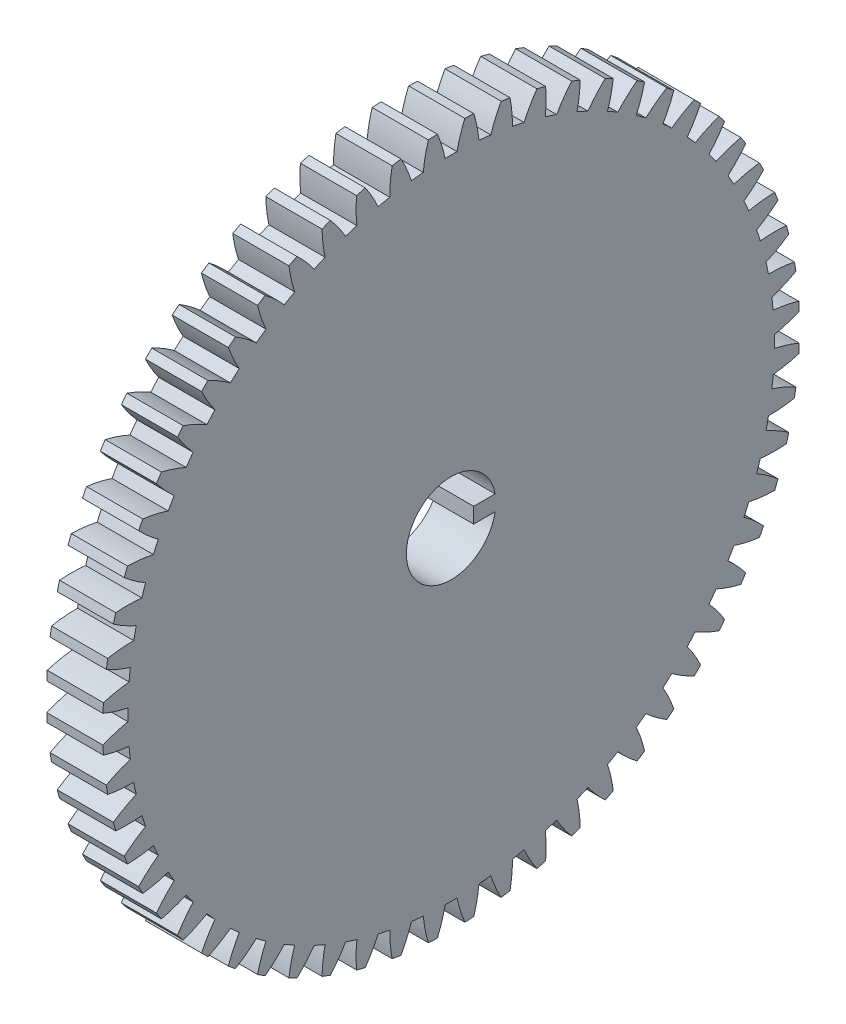
SolidWorks part; units mm, degrees
ref_plane "Plane1" through (0, 0, 0) normal (0, 0, 1) x (1, 0, 0)
ref_plane "Plane2" through (0, 0, 0) normal (0, 1, 0) x (1, 0, 0)
ref_plane "Plane3" through (0, 0, 0) normal (1, 0, 0) x (0, 0, -1)
sketch "HoldingSke" plane through (0, 0, 0) normal (0, 1, 0) x (1, 0, 0)
  line L0 (0, 0) -> (254, -439.9409)
  line L1 (-15, 0) -> (100, 0) construction
  line L2 (0, 0) -> (-2.1039, 2.3779)
  line L3 (0, 0) -> (-11.863, 4.5341)
  line L4 (0, 0) -> (4.318, 7.479)
  line L5 (0, 0) -> (-47.5972, -17.7524)
  line L6 (0, 0) -> (-5.2639, -3.5516)
  line L7 (-2.1039, 2.3779) -> (8.8308, 51.9871)
  line L8 (-76.2, 54.61) -> (-65.4837, 54.61)
  line L9 (-67.7845, 28.3722) -> (-49.3413, 33.142)
  line L10 (-76.2, 71.12) -> (104.1128, 71.12)
  line L11 (0, 0) -> (-6.35, 0)
  line L12 (-76.2, 101.6) -> (-76.1492, 101.6)
  line L13 (24.9733, 27.94) -> (52.9518, 28.4284)
  line L14 (24.9733, 27.94) -> (25.0241, 27.9398)
  line L15 (24.9733, 27.94) -> (100.4021, 29.52)
  circle A0 centre (0, 0) radius 4.7625
  circle A1 centre (0, 0) radius 36.5252
  circle A2 centre (0, 0) radius 38.1
  circle A3 centre (0, 0) radius 4.7625
  dimension "Num_teeth" = 60
  dimension "H" = 19.05
  dimension "Pitch_radius" = 180.3128
  dimension "Width" = 6.35
  dimension "Thickness" = 6.35
sketch "BasProSke" plane through (0, 0, 0) normal (0, 1, 0) x (1, 0, 0)
  line L0 (-10, 0) -> (60, 0) construction
  line L1 (0, 0) -> (0, 39.37)
  line L2 (0, 0) -> (6.35, 0)
  line L3 (6.35, 0) -> (6.35, 39.37)
  line L4 (6.35, 39.37) -> (0, 39.37)
  dimension "Thickness" = 6.35
  dimension "Diameter" = 78.74
revolve "Base-Revolve" add sketch "BasProSke" angle 360 about L0
sketch "TooCutSke" plane through (0, 0, 0) normal (1, 0, 0) x (0, 0, -1)
  line L1 (0, 0) -> (0, 107) construction
  line L2 (0, 0) -> (-1.0862, 38.0845) construction
  line L3 (0, 0) -> (-3.9869, 76.0739) construction
  line L4 (-1.0862, 38.0845) -> (-1.9934, 38.037) construction
  arc A0 (0.674, 36.519) -> (-0.674, 36.519) centre (0, 0) ccw
  arc A1 (1.5613, 39.3644) -> (-1.5613, 39.3644) centre (0, 0) ccw
  circle A2 centre (0, 0) radius 38.1 construction
  circle A3 centre (0, 0) radius 36.8864 construction
  arc A4 (-0.674, 36.519) -> (-1.5613, 39.3644) centre (-15.597, 33.4267) ccw
  arc A5 (1.5613, 39.3644) -> (0.674, 36.519) centre (15.597, 33.4267) ccw
extrude "ToothCut" cut sketch "TooCutSke" along normal through all
fillet "Breaks" [suppressed] radius 0.0254 tangent propagation no
fillet "RootFillets" [suppressed] radius 0.3048
pattern_circular "TeethCuts" count 60 every 6 about axis through (-10, 0, 0) along (1, 0, 0) of "ToothCut", "RootFillets", "Breaks"
sketch "HubNeaOneSke" plane through (0, 0, 0) normal (-1, 0, 0) x (0, 0, 1)
  circle A0 centre (0, 0) radius 36.5252
  dimension "Diameter" = 73.0504
extrude "HubNearOne" [suppressed] add sketch "HubNeaOneSke" along normal blind 44.4501
sketch "HubNeaBotSke" plane through (0, 0, 0) normal (-1, 0, 0) x (0, 0, 1)
  circle A0 centre (0, 0) radius 36.5252
  dimension "Diameter" = 73.0504
extrude "HubNearBoth" [suppressed] add sketch "HubNeaBotSke" along normal blind 22.225
ref_plane "FarPln" through (6.35, 0, 0) normal (1, 0, 0) x (0, 0, -1)
sketch "HubFarSke" plane through (6.35, 0, 0) normal (1, 0, 0) x (0, 0, -1)
  circle A0 centre (0, 0) radius 36.5252
  dimension "Diameter" = 73.0504
extrude "HubFar" [suppressed] add sketch "HubFarSke" along normal blind 22.225
sketch "BorSke" plane through (0, 0, 0) normal (1, 0, 0) x (0, 0, -1)
  circle A0 centre (0, 0) radius 5.05
  dimension "D1" = 10.1
extrude "Bore" cut sketch "BorSke" along normal mid plane 101.6001
sketch "KeySke" plane through (0, 0, 0) normal (1, 0, 0) x (0, 0, -1)
  line L0 (-1.1913, 0) -> (-1.1913, 5.9538)
  line L1 (-1.1913, 5.9538) -> (1.1913, 5.9538)
  line L2 (1.1913, 5.9538) -> (1.1913, 0)
  line L3 (0, 0) -> (0, 34) construction
  line L4 (-1.1913, 0) -> (1.1913, 0)
  dimension "Width" = 2.3825
extrude "Keyway" [suppressed] cut sketch "KeySke" along normal mid plane 101.6001
pattern_circular "Keyway2" [suppressed] count 2 every 90 about axis through (-10, 0, 0) along (1, 0, 0) reverse direction yes
sketch "Sketch1" plane through (6.35, 0, 0) normal (1, 0, 0) x (0, 0, -1)
  line L0 (5.05, 0) -> (2.55, 0) construction
  line L1 (2.55, -0.875) -> (2.55, 0.875)
  line L2 (2.55, 0.875) -> (4.9736, 0.875)
  line L3 (2.55, -0.875) -> (4.9736, -0.875)
  circle A0 centre (0, 0) radius 5.05 construction
  circle A1 centre (0, 0) radius 5.05
  point P8 (2.55, 0)
  dimension "D1" = 2.5
  dimension "D2" = 1.75
extrude "Boss-Extrude1" add sketch "Sketch1" against normal blind 6.35 contours L0 A1 L2 L1 | A1 L0 L1 L3 region at (6.35, -0.4353, -3.7874) region at (6.35, 0.4353, -3.7874)
equation "' \"Pitch@HoldingSke\" = 4"
equation "' \"Num_teeth@HoldingSke\" = 12"
equation "' \"Ap@HoldingSke\" =  20"
equation "' \"Ap@HoldingSke\" = 20"
equation "' \"Width@HoldingSke\" = 0.5"
equation "' \"Hub_dia@HoldingSke\"= 1"
equation "' \"Hub_dia@HoldingSke\" = 1"
equation "' \"Overall_len@HoldingSke\" = 1.0"
equation "' \"Bore@HoldingSke\" = 0.75"
equation "' \"T_dim@HoldingSke\" = 0.85"
equation "' \"Width@KeySke\" = 0.25"
equation "' \"Show_teeth@HoldingSke\" = 13"
equation "' \"Backlash@HoldingSke\" = 0.009"
equation "' \"Addendum_fac@HoldingSke\" = 1.0"
equation "' \"Dedendum_fac@HoldingSke\" = 1.25"
equation "' \"Dedendum_add@HoldingSke\" = 0.00005"
equation "' \"Clearance_fac@HoldingSke\" = 0.25"
equation "' \"Pitch@HoldingSke\" = 0.5"
equation "' \"Num_teeth@HoldingSke\" = 23"
equation "' \"Show_teeth@HoldingSke\" = 23"
equation "' \"Backlash@HoldingSke\" = 0.0375"
equation "\"Overcut_dia@TooCutSke\" = (\"Num_teeth@HoldingSke\" + 2 * \"Addendum_fac@HoldingSke\") / \"Pitch@HoldingSke\" + 0.002"
equation "\"Pitch_dia@TooCutSke\" = \"Num_teeth@HoldingSke\" / \"Pitch@HoldingSke\""
equation "\"Base_dia@TooCutSke\" = \"Num_teeth@HoldingSke\" / \"Pitch@HoldingSke\" * cos((\"Ap@HoldingSke\"  * 3.14159265 / 180))"
equation "\"Root_dia@TooCutSke\" = (\"Num_teeth@HoldingSke\" + 2) / \"Pitch@HoldingSke\" - 2 * (\"Addendum_fac@HoldingSke\" + \"Dedendum_fac@HoldingSke\") / \"Pitch@HoldingSke\" - \"Dedendum_add@HoldingSke\" * 2"
equation "\"Half_ang@TooCutSke\" = 180 / \"Num_teeth@HoldingSke\""
equation "\"Half_CT@TooCutSke\" = \"Num_teeth@HoldingSke\" / \"Pitch@HoldingSke\" * sin((3.14159265 / 2 / \"Num_teeth@HoldingSke\")) / 2 - 7 * \"Backlash@HoldingSke\" / 4"
equation "\"Flank_rad@TooCutSke\" = \"Num_teeth@HoldingSke\" / \"Pitch@HoldingSke\" / 5"
equation "\"Radius@RootFillets\" = \"Clearance_fac@HoldingSke\" / \"Pitch@HoldingSke\" + \"Dedendum_add@HoldingSke\""
equation "\"Break_rad@Breaks\" = 0.02 / \"Pitch@HoldingSke\""
equation "\"Thickness@HoldingSke\" = \"Width@HoldingSke\""
equation "\"OAL@HoldingSke\" = \"Thickness@HoldingSke\""
equation "\"MHD@HoldingSke\" = (\"Num_teeth@HoldingSke\" + 2) / \"Pitch@HoldingSke\" - 2 * (\"Addendum_fac@HoldingSke\" + \"Dedendum_fac@HoldingSke\")  / \"Pitch@HoldingSke\" - \"Dedendum_add@HoldingSke\" * 2"
equation "\"MBD@HoldingSke\" = (\"Num_teeth@HoldingSke\" + 2) / \"Pitch@HoldingSke\" - 2 * (\"Addendum_fac@HoldingSke\" + \"Dedendum_fac@HoldingSke\")  / \"Pitch@HoldingSke\" - \"Dedendum_add@HoldingSke\" * 2 - 0.002"
equation "\"MHD@HoldingSke\" = ((sgn( \"MHD@HoldingSke\" - \"Hub_dia@HoldingSke\" )-1)*( \"MHD@HoldingSke\" - \"Hub_dia@HoldingSke\" ))/-2+ \"Hub_dia@HoldingSke\""
equation "\"MBD@HoldingSke\" = ((sgn( \"MBD@HoldingSke\" - \"Bore@HoldingSke\" )-1)*( \"MBD@HoldingSke\" - \"Bore@HoldingSke\" ))/-2+ \"Bore@HoldingSke\""
equation "\"OAL@HoldingSke\" = ((sgn( \"OAL@HoldingSke\" - \"Overall_len@HoldingSke\" )+1)*( \"OAL@HoldingSke\" - \"Overall_len@HoldingSke\" ))/2 + \"Overall_len@HoldingSke\" + 0.000002"
equation "\"Num_teeth@TeethCuts\" = int( \"Show_teeth@HoldingSke\" ) + 1"
equation "\"Num_teeth@TeethCuts\" = ((sgn( \"Num_teeth@TeethCuts\" - \"Num_teeth@HoldingSke\" )-1)*( \"Num_teeth@TeethCuts\" - \"Num_teeth@HoldingSke\" ))/-2+ \"Num_teeth@HoldingSke\""
equation "\"Num_teeth@TeethCuts\" = ((sgn( \"Num_teeth@TeethCuts\" - 2.0)+1)*( \"Num_teeth@TeethCuts\" - 2.0))/2 +2.0"
equation "\"Angle@TeethCuts\" = 360.0 / \"Num_teeth@HoldingSke\""
equation "\"Diameter@BasProSke\" = (\"Num_teeth@HoldingSke\" + 2 * \"Addendum_fac@HoldingSke\") / \"Pitch@HoldingSke\""
equation "\"Thickness@BasProSke\"  = \"Thickness@HoldingSke\""
equation "' \"Fillet_rad@BasProSke\" =  \"Thickness@HoldingSke\" * 0.05"
equation "' \"Fillet_rad@BasProSke\" = \"Thickness@HoldingSke\" * 0.05"
equation "\"MHD@HoldingSke\" = ((sgn( \"MHD@HoldingSke\" - \"Root_dia@TooCutSke\" )-1)*( \"MHD@HoldingSke\" - \"Root_dia@TooCutSke\" ))/-2+ \"Root_dia@TooCutSke\""
equation "\"Diameter@HubNeaOneSke\" = \"MHD@HoldingSke\""
equation "\"Length@HubNearOne\" = \"OAL@HoldingSke\" - \"Thickness@BasProSke\""
equation "\"Diameter@HubNeaBotSke\" = \"MHD@HoldingSke\""
equation "\"Length@HubNearBoth\" = ( \"OAL@HoldingSke\" - \"Thickness@BasProSke\" ) / 2.0"
equation "\"Thickness@FarPln\" = \"Thickness@BasProSke\""
equation "\"Diameter@HubFarSke\" = \"MHD@HoldingSke\""
equation "\"Length@HubFar\" = ( \"OAL@HoldingSke\" - \"Thickness@BasProSke\" ) / 2.0"
equation "\"D1@Bore\" = \"OAL@HoldingSke\" * 2.0"
equation "\"D1@Keyway\" = \"OAL@HoldingSke\" * 2.0"
equation "\"Offset@KeySke\" = \"T_dim@HoldingSke\" - \"MBD@HoldingSke\" / 2.0"
